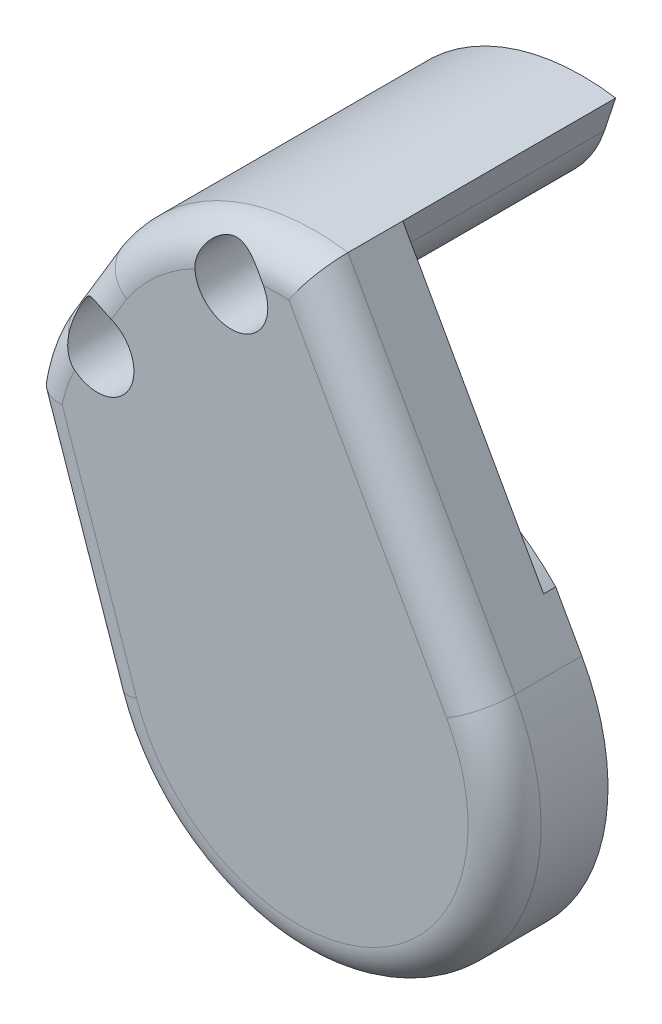
SolidWorks part; units mm, degrees
material "ABS"
ref_plane "Front Plane" through (0, 0, 0) normal (0, 0, 1) x (1, 0, 0)
ref_plane "Top Plane" through (0, 0, 0) normal (0, 1, 0) x (1, 0, 0)
ref_plane "Right Plane" through (0, 0, 0) normal (1, 0, 0) x (0, 0, -1)
sketch "Sketch1" plane through (0, 0, 0) normal (0, 0, 1) x (1, 0, 0)
  line L0 (-21.5118, -23.5649) -> (-14.5118, -23.5649)
  line L1 (0, -9.9671) -> (2.0631, -3.7458)
  line L3 (-15.6677, -11.5659) -> (-19.5301, -18.0027)
  arc A1 (-19.5301, -18.0027) -> (-21.5118, -23.5649) centre (-6.6677, -25.7195) ccw
  arc A2 (-15.6677, -11.5659) -> (2.0631, -3.7458) centre (-0.6677, -21.5651) cw
  arc A3 (-14.5118, -23.5649) -> (0, -9.9671) centre (21.0043, -46.9259) cw
  circle A4 centre (-4.5301, -8.0036) radius 1.8
  circle A5 centre (-15.5301, -18.0027) radius 1.8
  dimension "D1" = 7
  dimension "D8" = 3.6
  dimension "D2" = 2.0631
  dimension "D3" = 3.7458
  dimension "D4" = 16.9817
  dimension "D5" = 15.5614
  dimension "D6" = 5.9817
  dimension "D7" = 5.5622
extrude "Boss-Extrude1" add sketch "Sketch1" along normal blind 21
sketch "Sketch2" plane through (0, 0, 21) normal (0, 0, 1) x (1, 0, 0)
  line L0 (-15.6677, -11.5659) -> (-19.5301, -18.0027) construction
  line L1 (-15.6677, -11.5659) -> (-19.5301, -18.0027)
  line L2 (2.0631, -3.7458) -> (15.7796, -28.3476)
  line L3 (-21.5118, -23.5649) -> (-15.1513, -42.1348)
  arc A0 (-19.5301, -18.0027) -> (-21.5118, -23.5649) centre (-6.6677, -25.7195) ccw construction
  arc A1 (2.0631, -3.7458) -> (-15.6677, -11.5659) centre (-0.6677, -21.5651) ccw construction
  arc A2 (-19.5301, -18.0027) -> (-21.5118, -23.5649) centre (-6.6677, -25.7195) ccw
  arc A3 (2.0631, -3.7458) -> (-15.6677, -11.5659) centre (-0.6677, -21.5651) ccw
  arc A4 (15.7796, -28.3476) -> (-15.1513, -42.1348) centre (0.9315, -36.6261) cw
  circle A5 centre (-15.5301, -18.0027) radius 1.8 construction
  circle A6 centre (-4.5301, -8.0036) radius 1.8 construction
  circle A7 centre (-15.5301, -18.0027) radius 1.8
  circle A8 centre (-4.5301, -8.0036) radius 1.8
  dimension "D1" = 17
  dimension "D2" = 22.4433
  dimension "D3" = 13.0611
extrude "Boss-Extrude2" add sketch "Sketch2" along normal blind 4 and the other way blind 4.5
sketch "Sketch3" plane through (0, 0, 16.5) normal (0, 0, -1) x (-1, 0, 0)
  circle A0 centre (-0.9315, -36.6261) radius 11.25
  dimension "D1" = 22.5
  dimension "D2" = 32.8803
  dimension "D3" = 22.4433
extrude "Cut-Extrude1" cut sketch "Sketch3" against normal blind 7
sketch "Sketch4" plane through (0, 0, 16.5) normal (0, 0, -1) x (-1, 0, 0)
  circle A0 centre (-0.9315, -36.6261) radius 13
  dimension "D1" = 26
extrude "Cut-Extrude2" cut sketch "Sketch4" against normal blind 1.5
sketch "Sketch5" plane through (0, 0, 25) normal (0, 0, 1) x (1, 0, 0)
  circle A0 centre (-4.5301, -8.0036) radius 3
  circle A1 centre (-15.5301, -18.0027) radius 3
  dimension "D1" = 6
extrude "Cut-Extrude3" cut sketch "Sketch5" against normal blind 12
fillet "Fillet1" radius 3 6 edges at (-20.7974, -20.6853, 25) (8.9213, -16.0467, 25) (7.8526, -52.1534, 25) (-17.5989, -14.7843, 25) (-7.9425, -5.0708, 25) (-18.3315, -32.8499, 25)
sketch "Sketch6" plane through (0, 0, 16.5) normal (0, 0, -1) x (-1, 0, 0)
  line L0 (-2.0631, -3.7458) -> (0, -9.9671)
  line L1 (-2.0631, -3.7458) -> (-13.6368, -24.5042)
  line L2 (-15.7796, -28.3476) -> (-2.0631, -3.7458) construction
  line L3 (10.6831, -18.5879) -> (8.6095, -21.8839)
  arc A0 (-13.6368, -24.5042) -> (8.6095, -21.8839) centre (-0.9315, -36.6261) cw
  arc A1 (0, -9.9671) -> (10.6831, -18.5879) centre (-21.0043, -46.9259) cw
  arc A2 (14.5118, -23.5649) -> (0, -9.9671) centre (-21.0043, -46.9259) ccw construction
  dimension "D1" = 42.5104
  dimension "D2" = 17.5603
  dimension "D3" = 3.2959
  dimension "D4" = 10.6831
  dimension "D5" = 2.0736
  dimension "D6" = 11.5737
extrude "Cut-Extrude4" cut sketch "Sketch6" against normal blind 1
fillet "Fillet2" radius 10 2 edges at (-14.5118, -23.5649, 8.25) (0, -9.9671, 8.75)
